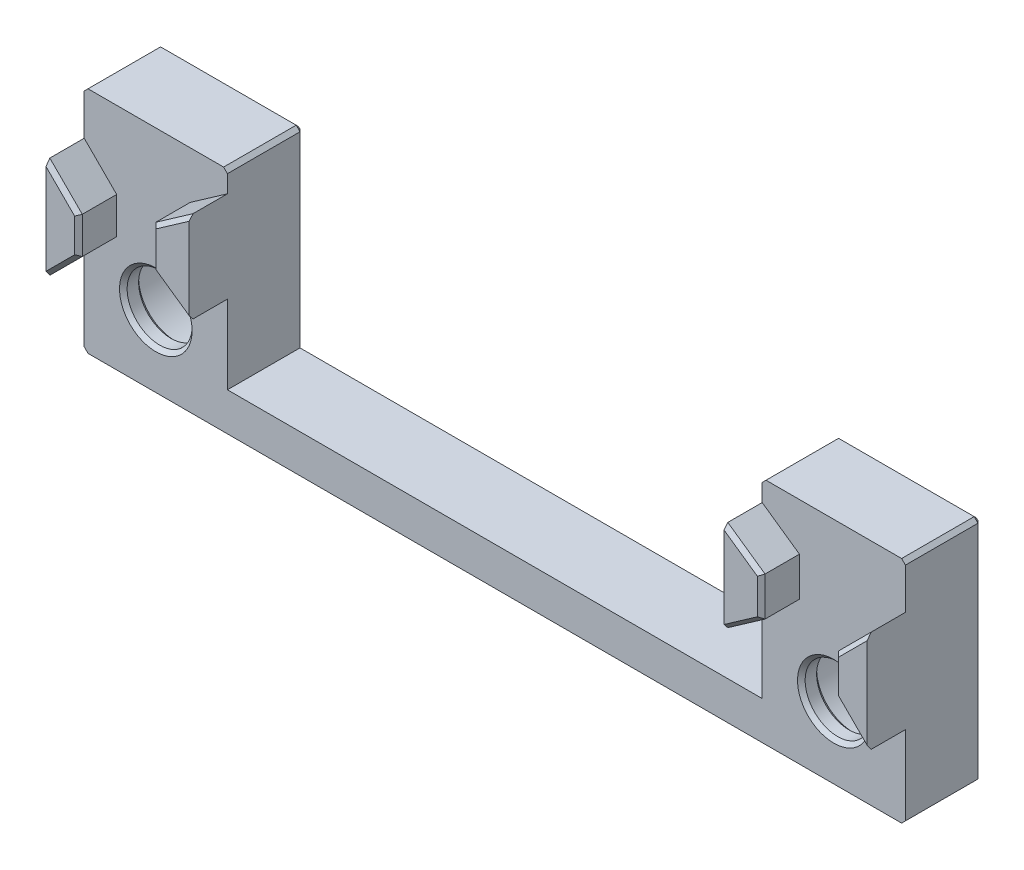
SolidWorks part; units mm, degrees
ref_plane "Front" through (0, 0, 0) normal (0, 0, 1) x (1, 0, 0)
ref_plane "Top" through (0, 0, 0) normal (0, 1, 0) x (1, 0, 0)
ref_plane "Right" through (0, 0, 0) normal (1, 0, 0) x (0, 0, -1)
sketch "Sketch1" plane through (0, 0, 0) normal (0, 0, 1) x (1, 0, 0)
  line L0 (-21.3, -6) -> (21.3, -6)
  line L5 (21.5, -5.8) -> (21.5, 5.8)
  line L6 (21.3, 6) -> (14.2, 6)
  line L7 (14, 5.8) -> (14, -4)
  line L8 (14, -4) -> (-14, -4)
  line L9 (-14, -4) -> (-14, 5.8)
  line L10 (-14.2, 6) -> (-21.3, 6)
  line L11 (-21.5, 5.8) -> (-21.5, -5.8)
  line L12 (21.5, 5.8) -> (21.5, -5.8) construction
  line L13 (21.3, 6) -> (14, 6) construction
  line L14 (21.3, -6) -> (-21.3, -6) construction
  line L15 (21.5, 5.8) -> (21.3, 6)
  line L16 (-14, 6) -> (-21.3, 6) construction
  line L17 (-21.5, 5.8) -> (-21.5, -5.8) construction
  line L18 (14.2, 6) -> (14, 5.8)
  line L19 (21.3, -6) -> (21.5, -5.8)
  line L20 (-21.5, -5.8) -> (-21.3, -6)
  line L21 (-21.3, 6) -> (-21.5, 5.8)
  line L22 (-14, 5.8) -> (-14.2, 6)
  point P0 (-21.5, -6)
  point P1 (21.5, -6)
  point P2 (21.5, 6)
  point P4 (14, 6)
  point P6 (-21.5, 6)
  point P13 (-14, 6)
  dimension "D1" = 45
  dimension "D3" = 45
  dimension "D6" = 0.2
  dimension "D5" = 45
  dimension "D7" = 45
  dimension "D12" = 0.2
  dimension "D8" = 45
  dimension "D11" = 0.2
  dimension "D9" = 0.2
  dimension "D10" = 45
  dimension "D2" = 0.2
  dimension "D4" = 0.2
extrude "Boss-Extrude1" add sketch "Sketch1" against normal blind 4
sketch "Sketch3" plane through (0, 0, 0) normal (0, 0, 1) x (1, 0, 0)
  line L1 (13.75, -0.0624) -> (15.95, 1.4781) construction
  line L7 (15.95, 1.4781) -> (15.95, 3.5219) construction
  line L8 (15.95, 3.5219) -> (13.75, 5.0624) construction
  line L9 (13.75, 5.0624) -> (11.55, 3.5219) construction
  line L10 (11.55, 3.5219) -> (11.55, 1.4781) construction
  line L11 (11.55, 1.4781) -> (13.75, -0.0624) construction
  line L12 (16.1, 1.4) -> (16.1, 3.6)
  line L13 (16.1, 3.6) -> (13.75, 5.2455)
  line L14 (13.75, 5.2455) -> (11.4, 3.6)
  line L16 (11.4, 3.6) -> (11.4, 1.4)
  line L30 (11.4, 1.4) -> (13.75, -0.2455)
  line L32 (13.75, -0.2455) -> (16.1, 1.4)
  line L36 (16.1, 1.4) -> (16.1, 3.6) construction
  line L46 (16.1, 3.6) -> (13.75, 5.2455) construction
  line L47 (13.75, 5.2455) -> (11.4, 3.6) construction
  line L48 (11.4, 3.6) -> (11.4, 1.4) construction
  line L49 (11.4, 1.4) -> (13.75, -0.2455) construction
  line L50 (13.75, -0.2455) -> (16.1, 1.4) construction
  line L51 (14, 4.8874) -> (14, 0.1126)
  line L52 (14, 0.1126) -> (15.95, 1.4781)
  line L53 (15.95, 1.4781) -> (15.95, 3.5219)
  line L54 (15.95, 3.5219) -> (14, 4.8874)
  line L55 (14, 6) -> (14, 5.0705) construction
  line M6 (14, 5.8) -> (14, -4)
  dimension "D1" = 0
  dimension "D2" = 0.15
extrude "Slot Aligner" add sketch "Sketch3" along normal blind 2 contours L53 L54 L52 M6 region at (14.8448, 2.5, 0)
mirror "Mirror3" about plane through (0, 0, 0) normal (1, 0, 0) of "Slot Aligner"
sketch "Sketch4" plane through (0, 0, 0) normal (0, 0, -1) x (-1, 0, 0)
  line L8 (-19.8, 1.9586) -> (-21.4, 3.5586)
  line L10 (-21.4, -1.5586) -> (-19.8, 0.0414)
  line L11 (-19.8, 0.0414) -> (-19.8, 1.9586)
  line L21 (-21.5, -1.8) -> (-19.7, 0)
  line L25 (-19.7, 0) -> (-19.7, 2)
  line L26 (-19.7, 2) -> (-21.5, 3.8)
  line L27 (-21.5, 3.8) -> (-21.5, -1.8)
  line L28 (-21.5, -1.8) -> (-19.7, 0) construction
  line L29 (-19.7, 0) -> (-19.7, 2) construction
  line L30 (-19.7, 2) -> (-21.5, 3.8) construction
  line L31 (-21.5, 3.8) -> (-21.5, -1.8) construction
  line L32 (-21.4, 3.5586) -> (-21.5, 3.6586)
  line L33 (-21.5, 3.6586) -> (-21.5, -1.6586)
  line L34 (-21.5, -1.6586) -> (-21.4, -1.5586)
  line L36 (-21.4, 3.5586) -> (-21.4, -1.5586) construction
  dimension "D1" = 0
  dimension "D2" = 0.1
extrude "Aligner" add sketch "Sketch4" against normal blind 2
mirror "Aligners" about plane through (0, 0, 0) normal (1, 0, 0) of "Aligner"
chamfer "Deburs" distance 0.2 angle 45 26 edges at (14, 0.9, -4) (14.1, 5.9, -4) (17.75, 6, -4) (21.4, 5.9, -4) (21.5, 0, -4) (21.4, -5.9, -4) (0, -6, -4) (-21.4, -5.9, -4) (-21.5, 0, -4) (-21.4, 5.9, -4) (-17.75, 6, -4) (-14.1, 5.9, -4) (-14, 0.9, -4) (0, -4, -4) (20.65, -0.8086, 2) (20.65, 2.8086, 2) (19.8, 1, 2) (14.975, 4.2047, 2) (15.95, 2.5, 2) (14.975, 0.7953, 2) (-14.975, 4.2047, 2) (-15.95, 2.5, 2) (-14.975, 0.7953, 2) (-20.65, 2.8086, 2) (-19.8, 1, 2) (-20.65, -0.8086, 2)
sketch "Sketch5" plane through (0, 0, -4) normal (0, 0, -1) x (-1, 0, 0)
  point P0 (-17.75, -2.25)
  point P1 (17.75, -2.25)
hole_wizard "CBORE for M3 SHCS1" positions "Sketch5" profile "Sketch6" counterbore size "M3" standard "ANSI Metric" end condition through all
sketch "Sketch6" plane through (17.75, -2.25, -4) normal (1, 0, 0) x (0, 1, 0)
  line L0 (0, 0) -> (0, 6)
  line L1 (0, 6) -> (1.7, 6)
  line L3 (1.7, 6) -> (1.7, 3)
  line L4 (1.7, 3) -> (3.25, 3)
  line L5 (3.25, 3) -> (3.25, 0)
  line L7 (3.25, 0) -> (0, 0)
  line L11 (0, -6.35) -> (0, 107.95) construction
  dimension "Thru Hole Dia." = 3.4
  dimension "Thru Hole Depth" = 6
  dimension "C'Bore Dia." = 6.5
  dimension "C'Bore Depth" = 3
chamfer "Chamfer1" distance 0.2 angle 45 6 edges at (-19.45, -2.25, 0) (-19.45, -2.25, -1) (16.05, -2.25, 0) (16.05, -2.25, -1) (14.5, -2.25, -4) (-21, -2.25, -4)
